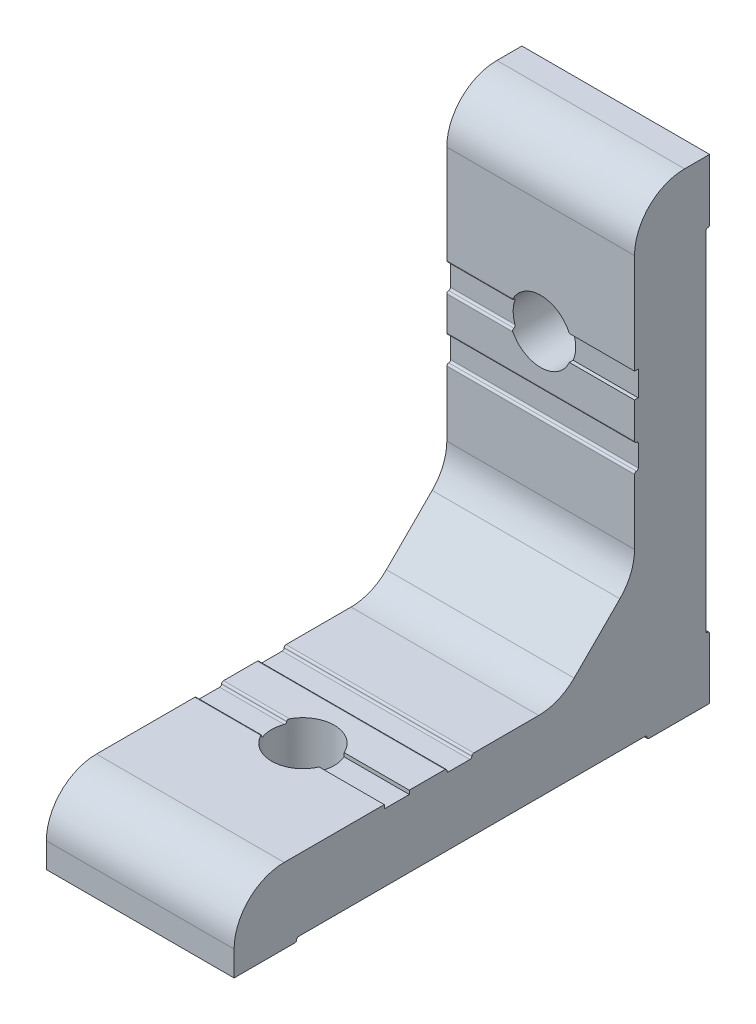
SolidWorks part; units mm, degrees
ref_plane "Plano frontal" through (0, 0, 0) normal (0, 0, 1) x (1, 0, 0)
ref_plane "Plano superior" through (0, 0, 0) normal (0, 1, 0) x (1, 0, 0)
ref_plane "Plano direito" through (0, 0, 0) normal (1, 0, 0) x (0, 0, -1)
ref_plane "Plano1" through (10, 0, 0) normal (1, 0, 0) x (0, 0, -1)
sketch "Esboço1" plane through (10, 0, 0) normal (1, 0, 0) x (0, 0, -1)
  line L0 (7, 38) -> (-31, 38)
  line L1 (-31, 38) -> (-31, 0)
  line L2 (-31, 0) -> (7, 0)
  line L3 (7, 0) -> (7, 38)
  dimension "D1" = 38
extrude "Ressalto-extrusão1" add sketch "Esboço1" against normal blind 15
sketch "Esboço2" plane through (-5, 0, 0) normal (-1, 0, 0) x (0, 0, 1)
  line L0 (31, 38) -> (-1, 38)
  line L1 (-1, 38) -> (-1, 12)
  line L2 (-1, 12) -> (5, 6)
  line L3 (5, 6) -> (31, 6)
  line L4 (31, 6) -> (31, 38)
  line L5 (31, 0) -> (-7, 0) construction
  line L6 (-7, 0) -> (-7, 38) construction
  line L7 (-7, 38) -> (31, 38) construction
  dimension "D1" = 6
  dimension "D2" = 6
  dimension "D3" = 6
  dimension "D4" = 6
extrude "Corte-extrusão1" cut sketch "Esboço2" against normal through all
sketch "Esboço7" plane through (10, 0, 0) normal (1, 0, 0) x (0, 0, -1)
  line L0 (7, 0) -> (7, 38) construction
  line L1 (7, 33) -> (6.7, 33)
  line L2 (7, 33) -> (7, 5)
  line L3 (7, 5) -> (6.7, 5)
  line L4 (6.7, 33) -> (6.7, 5)
  line L5 (-31, 0) -> (7, 0) construction
  line L6 (2, 0) -> (-26, 0)
  line L7 (2, 0) -> (2, 0.3)
  line L8 (2, 0.3) -> (-26, 0.3)
  line L9 (-26, 0) -> (-26, 0.3)
  line L10 (7, 38) -> (1, 38) construction
  line L11 (-31, 6) -> (-31, 0) construction
  line L12 (-5, 6) -> (-31, 6) construction
  line L13 (-14, 6) -> (-12, 6)
  line L14 (-14, 6) -> (-14, 5.7)
  line L15 (-14, 5.7) -> (-12, 5.7)
  line L16 (-12, 6) -> (-12, 5.7)
  line L17 (1, 38) -> (1, 12) construction
  line L18 (1, 21) -> (1.3, 21)
  line L19 (1, 21) -> (1, 19)
  line L20 (1, 19) -> (1.3, 19)
  line L21 (1.3, 21) -> (1.3, 19)
  line L22 (-19, 6) -> (-19, 5.7)
  line L23 (-17, 6) -> (-17, 5.7)
  line L24 (-19, 6) -> (-17, 6)
  line L25 (-19, 5.7) -> (-17, 5.7)
  line L26 (1.3, 26) -> (1.3, 24)
  line L27 (1, 26) -> (1, 24)
  line L28 (1, 26) -> (1.3, 26)
  line L29 (1, 24) -> (1.3, 24)
  point P28 (-13, 5.7)
  point P29 (1.3, 20)
  point P34 (-18, 5.7)
  point P39 (1.3, 25)
  dimension "D1" = 5
  dimension "D2" = 5
  dimension "D3" = 5
  dimension "D4" = 5
  dimension "D5" = 0.3
  dimension "D6" = 0.3
  dimension "D7" = 2
  dimension "D8" = 0.3
  dimension "D9" = 2
  dimension "D10" = 0.3
  dimension "D11" = 20
  dimension "D12" = 20
extrude "Corte-extrusão2" cut sketch "Esboço7" against normal through all
hole_wizard "Furo de diâmetro Ø7.0 (7)3" positions "Esboço4" profile "Esboço3" hole size "Ø7.0" standard "Ansi Metric" end condition through all
sketch "Esboço4" plane through (0, 6, 0) normal (0, 1, 0) x (1, 0, 0)
  line L0 (10, -31) -> (-5, -31) construction
  line L1 (-5, 7) -> (10, 7) construction
  point P0 (2.5, -18)
  point P3 (2.5, -31)
  dimension "D1" = 25
sketch "Esboço3" plane through (2.5, 6, 18) normal (1, 0, 0) x (0, 0, 1)
  line L0 (0, 0) -> (0, 6)
  line L1 (0, 6) -> (2.5, 6)
  line L2 (2.5, 6) -> (2.5, 0)
  line L5 (2.5, 0) -> (0, 0)
  line L11 (0, -6.35) -> (0, 107.95) construction
  dimension "Thru Hole Dia." = 5
  dimension "Thru Hole Depth" = 6
hole_wizard "Furo de diâmetro Ø7.0 (7)2" positions "Esboço6" profile "Esboço5" hole size "Ø7.0" standard "Ansi Metric" end condition through all
sketch "Esboço6" plane through (0, 0, -7) normal (0, 0, -1) x (-1, 0, 0)
  line L0 (5, 38) -> (-10, 38) construction
  line L1 (5, 0) -> (-10, 0) construction
  point P0 (-2.5, 25)
  point P3 (-2.5, 38)
  dimension "D1" = 25
sketch "Esboço5" plane through (2.5, 25, -7) normal (1, 0, 0) x (0, 1, 0)
  line L0 (0, 0) -> (0, 38)
  line L1 (0, 38) -> (2.5, 38)
  line L2 (2.5, 38) -> (2.5, 0)
  line L5 (2.5, 0) -> (0, 0)
  line L11 (0, -6.35) -> (0, 107.95) construction
  dimension "Thru Hole Dia." = 5
  dimension "Thru Hole Depth" = 38
fillet "Filete1" radius 4 4 edges at (2.5, 6, 31) (2.5, 6, 5) (2.5, 38, -1) (2.5, 12, -1)
fillet "Filete2" radius 0.15 24 edges at (2.5, 5, -7) (2.5, 5, -6.7) (2.5, 33, -7) (2.5, 33, -6.7) (2.5, 0, 26) (2.5, 0.3, 26) (2.5, 0.3, -2) (2.5, 0, -2) (2.5, 19, -1.3) (2.5, 19, -1) (2.5, 21, -1.3) (2.5, 21, -1) (2.5, 5.7, 14) (2.5, 6, 14) (2.5, 5.7, 12) (2.5, 6, 12) (-2.3956, 26, -1.3) (-2.3956, 24, -1.3) (-2.3956, 24, -1) (-2.3956, 26, -1) (-2.3956, 5.7, 19) (-2.3956, 5.7, 17) (-2.3956, 6, 17) (-2.3956, 6, 19)
ref_plane "Plano2" [suppressed] through (2.5, 0, 0) normal (-1, 0, 0) x (0, 0, 1)
equation "\"D2@Esboço2\"=\"D1@Esboço2\""
